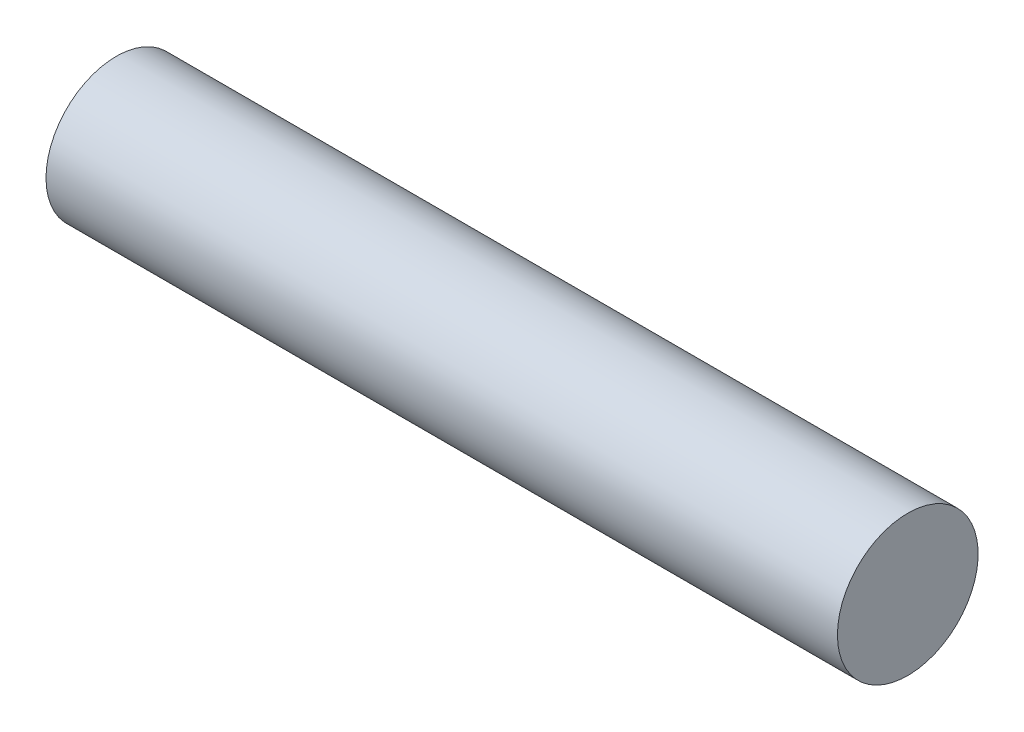
SolidWorks part; units mm, degrees
ref_plane "Front Plane" through (0, 0, 0) normal (0, 0, 1) x (1, 0, 0)
ref_plane "Top Plane" through (0, 0, 0) normal (0, 1, 0) x (1, 0, 0)
ref_plane "Right Plane" through (0, 0, 0) normal (1, 0, 0) x (0, 0, -1)
ref_axis "X" through (-88.99, 0, 0) along (1, 0, 0)
ref_axis "Y" through (0, 0, -88.99) along (0, 0, 1)
ref_axis "Z" through (0, 55, 0) along (0, -1, 0)
sketch "Sketch1" plane through (0, 0, 0) normal (0, 0, 1) x (1, 0, 0)
  line L0 (-20.2222, 0) -> (12.2963, 0) construction
  line L1 (0, 0) -> (0, 4)
  line L2 (0, 4) -> (45, 4)
  line L3 (45, 4) -> (45, 0)
  line L4 (45, 0) -> (0, 0)
  dimension "D1" = 8
  dimension "D2" = 45
revolve "Revolve1" add sketch "Sketch1" angle 360 about L0
